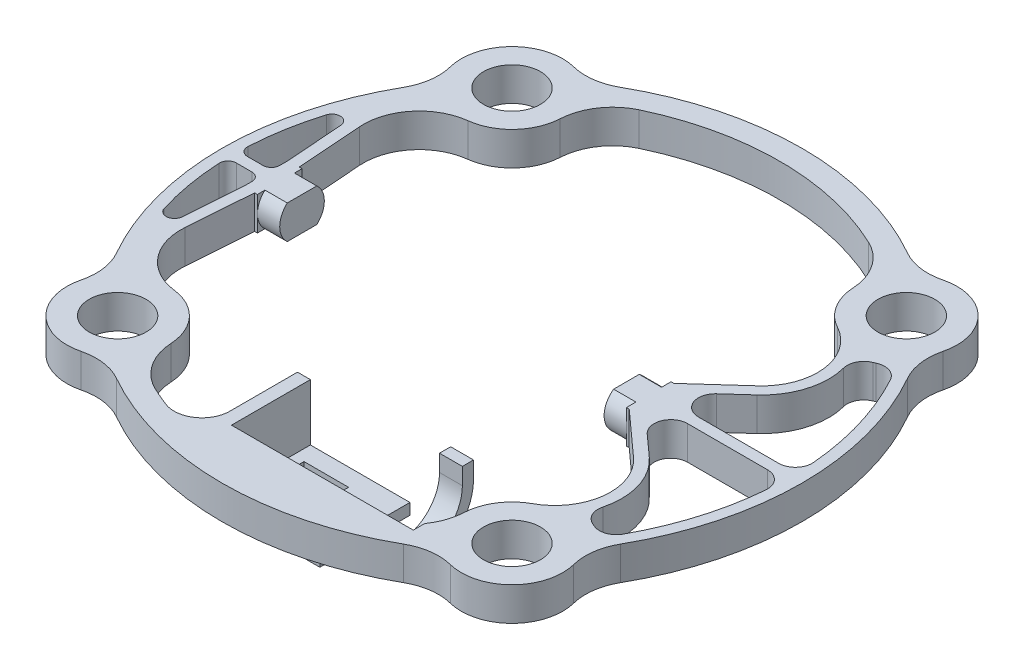
SolidWorks part; units mm, degrees
other "Markup1"
sketch "Sketch20" plane through (52, 6, -52) normal (0.9882, 0.0434, -0.1465) x (-0.1478, 0.0276, -0.9886)
ref_plane "Front Plane" through (0, 0, 0) normal (0, 0, 1) x (1, 0, 0)
ref_plane "Top Plane" through (0, 0, 0) normal (0, 1, 0) x (1, 0, 0)
ref_plane "Right Plane" through (0, 0, 0) normal (1, 0, 0) x (0, 0, -1)
sketch "Sketch1" plane through (0, 0, 0) normal (0, 1, 0) x (1, 0, 0)
  line L1 (-35.3553, -35.3553) -> (35.3553, -35.3553) construction
  line L2 (-35.3553, -35.3553) -> (-35.3553, 35.3553) construction
  line L3 (-35.3553, 35.3553) -> (35.3553, 35.3553) construction
  line L4 (35.3553, -35.3553) -> (35.3553, 35.3553) construction
  line L5 (-35.3553, -35.3553) -> (35.3553, 35.3553) construction
  line L6 (-35.3553, 35.3553) -> (35.3553, -35.3553) construction
  circle A0 centre (0, 0) radius 52
  circle A1 centre (0, 0) radius 48
  circle A2 centre (0, 0) radius 50 construction
  circle A3 centre (35.3553, 35.3553) radius 5.1
  circle A4 centre (-35.3553, 35.3553) radius 5.1
  circle A5 centre (-35.3553, -35.3553) radius 5.1
  circle A6 centre (35.3553, -35.3553) radius 5.1
  circle A7 centre (35.3553, 35.3553) radius 9.1
  circle A8 centre (-35.3553, 35.3553) radius 9.1
  circle A9 centre (-35.3553, -35.3553) radius 9.1
  circle A10 centre (35.3553, -35.3553) radius 9.1
  dimension "D1" = 96
  dimension "D2" = 104
  dimension "D3" = 100
  dimension "D4" = 10.2
  dimension "D5" = 10.2
  dimension "D6" = 10.2
  dimension "D7" = 10.2
  dimension "D8" = 4
extrude "Boss-Extrude1" add sketch "Sketch1" along normal blind 6 contours A8 A1 A7 A0 | A1 A8 A0 A4 | A0 A8 A4 | A0 A8 A1 A4 | A1 A8 A4 | A9 A1 A8 A0 | A1 A9 A5 | A1 A9 A0 A5 | A0 A9 A5 | A0 A9 A1 A5 | A10 A1 A9 A0 | A1 A10 A6 | A0 A10 A1 A6 | A0 A10 A6 | A1 A10 A0 A6 | A10 A0 A7 A1 | A0 A7 A3 | A0 A7 A1 A3 | A1 A7 A0 A3 | A1 A7 A3 region at (49.0102, 0, 15.4585) region at (39.943, 0, -30.075) region at (39.073, 0, -39.073) region at (39.073, 0, 39.073) region at (39.943, 0, 30.075) region at (31.3721, 0, -31.3721) region at (31.3721, 0, 31.3721) region at (30.075, 0, -39.943) region at (0, 0, -48.6096) region at (30.075, 0, 39.943) region at (0, 0, 51.3904) region at (-31.3721, 0, -31.3721) region at (-30.075, 0, -39.943) region at (-39.073, 0, -39.073) region at (-39.073, 0, 39.073) region at (-30.075, 0, 39.943) region at (-31.3721, 0, 31.3721) region at (-41.5843, 0, -27.9071) region at (-39.943, 0, -30.075) region at (-39.943, 0, 30.075)
fillet "Fillet1" radius 10 16 edges at (-27.2586, 3, 39.5091) (-39.5091, 3, 27.2586) (39.5091, 3, 27.2586) (27.2586, 3, 39.5091) (-39.5091, 3, -27.2586) (-27.2586, 3, -39.5091) (27.2586, 3, -39.5091) (39.5091, 3, -27.2586) (-42.5896, 3, 29.8349) (-29.8349, 3, 42.5896) (29.8349, 3, 42.5896) (42.5896, 3, 29.8349) (42.5896, 3, -29.8349) (29.8349, 3, -42.5896) (-29.8349, 3, -42.5896) (-42.5896, 3, -29.8349)
sketch "Sketch2" plane through (0, 6, 0) normal (0, 1, 0) x (1, 0, 0)
  line L0 (-41.15, 11.9734) -> (-41.15, -15.376) construction
  line L1 (24.02, 8.956) -> (24.02, -12.6154) construction
  line L2 (-47.833, 4) -> (47.833, 4) construction
  line L3 (-47.833, -4) -> (47.833, -4) construction
  line L4 (-47.833, 4) -> (-37.65, 4)
  line L5 (-37.65, 4) -> (-37.65, -4)
  line L6 (-37.65, -4) -> (-47.833, -4)
  line L7 (47.833, 4) -> (20.52, 4)
  line L8 (20.52, 4) -> (20.52, -4)
  line L9 (20.52, -4) -> (47.833, -4)
  arc A0 (-43.3702, 20.5675) -> (-43.3702, -20.5675) centre (0, 0) ccw construction
  arc A1 (43.3702, -20.5675) -> (43.3702, 20.5675) centre (0, 0) ccw construction
  arc A2 (-47.833, 4) -> (-47.833, -4) centre (0, 0) ccw
  arc A3 (47.833, 4) -> (47.833, -4) centre (0, 0) cw
  arc M11 (-43.3702, -20.5675) -> (-43.3702, 20.5675) centre (0, 0) cw
  arc M19 (43.3702, 20.5675) -> (43.3702, -20.5675) centre (0, 0) cw
  dimension "D1" = 41.15
  dimension "D2" = 24.02
  dimension "D3" = 4
  dimension "D4" = 4
  dimension "D5" = 3.5
  dimension "D6" = 3.5
extrude "Boss-Extrude2" add sketch "Sketch2" against normal up to surface (6 mm away) contours L6 L5 L4 M11 | L8 L9 L7 M19 region at (-42.7973, 6, 0) region at (34.2322, 6, 0) up to face at (0, 0, 0)
sketch "Sketch3" plane through (0, 6, 0) normal (0, 1, 0) x (1, 0, 0)
  line L0 (-42.15, 4) -> (-42.15, -4)
  line L2 (-47.833, 4) -> (-37.65, 4) construction
  line L3 (-37.65, -4) -> (-47.833, -4) construction
  line L4 (25.02, 4) -> (25.02, -4)
  line L5 (47.833, 4) -> (20.52, 4) construction
  line L6 (20.52, -4) -> (47.833, -4) construction
  line L7 (-37.65, 4) -> (-37.65, -4) construction
  line L8 (20.52, 4) -> (20.52, -4) construction
  line L9 (-42.15, 4) -> (-43.3702, 20.5675)
  line L10 (-42.15, -4) -> (-43.3702, -20.5675)
  line L11 (25.02, 4) -> (43.3702, 20.5675)
  line L12 (25.02, -4) -> (43.3702, -20.5675)
  arc A0 (-43.3702, 20.5675) -> (-43.3702, -20.5675) centre (0, 0) ccw
  arc A1 (43.3702, 20.5675) -> (43.3702, -20.5675) centre (0, 0) cw
  arc A2 (43.3702, -20.5675) -> (47.833, -4) centre (0, 0) ccw construction
  arc M7 (-43.3702, -20.5675) -> (-47.833, -4) centre (0, 0) cw
  line M8 (-47.833, -4) -> (-37.65, -4)
  line M10 (-37.65, 4) -> (-47.833, 4)
  arc M11 (-47.833, 4) -> (-43.3702, 20.5675) centre (0, 0) cw
  arc M19 (43.3702, 20.5675) -> (47.833, 4) centre (0, 0) cw
  line M20 (47.833, 4) -> (20.52, 4)
  line M22 (20.52, -4) -> (47.833, -4)
  arc M23 (47.833, -4) -> (43.3702, -20.5675) centre (0, 0) cw
  dimension "D1" = 4.5
  dimension "D2" = 4.5
extrude "Boss-Extrude3" add sketch "Sketch3" along direction (0, 1, 0) on the side against the normal up to surface (6 mm away) contours L9 M10 M11 | L10 M8 M7 | L11 M20 M19 | L12 M22 M23 region at (-44.6805, 6, -9.9724) region at (-44.6805, 6, 9.9724) region at (39.0615, 6, -9.6497) region at (39.0615, 6, 9.6497) up to face at (-1.4275, 0, 0)
sketch "Sketch4" plane through (0, 6, 0) normal (0, 1, 0) x (1, 0, 0)
  line L0 (-45.0759, 16.4974) -> (-44.3027, 6)
  line L1 (-44.3027, 6) -> (-47.6235, 6)
  line L2 (-47.6235, -6) -> (-44.3027, -6)
  line L3 (-44.3027, -6) -> (-45.0759, -16.4974)
  line L4 (-42.15, -4) -> (-43.3702, -20.5675) construction
  line L5 (-42.15, 4) -> (-43.3702, 20.5675) construction
  line L6 (-42.15, 4) -> (-37.65, 4) construction
  line L7 (-37.65, -4) -> (-42.15, -4) construction
  line L8 (44.2293, 18.6486) -> (30.2197, 6)
  line L9 (30.2197, 6) -> (47.6235, 6)
  line L10 (44.2293, -18.6486) -> (30.2197, -6)
  line L11 (30.2197, -6) -> (47.6235, -6)
  line L12 (25.02, 4) -> (20.52, 4) construction
  line L13 (25.02, 4) -> (43.3702, 20.5675) construction
  line L14 (25.02, -4) -> (43.3702, -20.5675) construction
  line L15 (20.52, -4) -> (25.02, -4) construction
  circle A0 centre (0, 0) radius 48
  dimension "D5" = 96
  dimension "D1" = 2
  dimension "D2" = 2
  dimension "D3" = 2
  dimension "D4" = 2
  dimension "D6" = 2
  dimension "D7" = 2
  dimension "D8" = 2
  dimension "D9" = 2
fillet "Fillet2" radius 10 4 edges at (43.3702, 3, 20.5675) (43.3702, 3, -20.5675) (-43.3702, 3, 20.5675) (-43.3702, 3, -20.5675)
sketch "Sketch5" plane through (0, 6, 0) normal (0, 1, 0) x (1, 0, 0)
  line L0 (32.939, 11.1497) -> (34.2793, 9.6652)
  line L1 (34.2793, 9.6652) -> (27.02, 3.1112)
  line L2 (32.939, -11.1497) -> (34.2793, -9.6652)
  line L3 (34.2793, -9.6652) -> (27.02, -3.1112)
  line L4 (27.02, -3.1112) -> (27.02, 3.1112)
  circle A0 centre (35.3553, 35.3553) radius 9.1
  circle A1 centre (35.3553, -35.3553) radius 9.1
  circle A2 centre (35.3553, -35.3553) radius 11.1
  circle A3 centre (35.3553, 35.3553) radius 11.1
  circle A4 centre (0, 0) radius 50
  circle A5 centre (26.2377, 18.5721) radius 12
  circle A6 centre (26.2377, -18.5721) radius 12
  arc A7 (45.1856, -25.7344) -> (45.1856, 25.7344) centre (0, 0) ccw construction
  arc A8 (32.939, 11.1497) -> (31.0113, 27.3591) centre (26.2377, 18.5721) ccw construction
  arc A9 (31.0113, -27.3591) -> (32.939, -11.1497) centre (26.2377, -18.5721) ccw construction
  dimension "D1" = 2
  dimension "D2" = 2
  dimension "D3" = 2
  dimension "D4" = 2
  dimension "D5" = 2
  dimension "D6" = 2
extrude "Cut-Extrude2" cut sketch "Sketch5" against normal blind 6 contours A6 A2 A4 A3 A5 L1 L4 L3 region at (40.5745, 6, 0)
sketch "Sketch6" plane through (0, 6, 0) normal (0, 1, 0) x (1, 0, 0)
  line L0 (27.02, 0.9819) -> (49.9904, 0.9819)
  line L1 (27.02, -3.1112) -> (27.02, 3.1112) construction
  line L2 (27.02, -1.0181) -> (49.9896, -1.0181)
  line L3 (27.02, 0.9819) -> (27.02, -1.0181)
  line L4 (49.9904, 0.9819) -> (51.1942, 0.9819)
  line L5 (51.1942, 0.9819) -> (51.1942, -1.0181)
  line L6 (51.1942, -1.0181) -> (49.9896, -1.0181)
  arc A0 (42.2845, -26.6837) -> (42.2845, 26.6837) centre (0, 0) ccw construction
  dimension "D1" = 2
extrude "Boss-Extrude4" add sketch "Sketch6" against normal up to surface (6 mm away) up to face at (-35.3553, 0, -30.2553)
fillet "Fillet3" radius 3 8 edges at (27.02, 3, -0.9819) (27.02, 3, 1.0181) (36.7582, 3, 24.3443) (42.2845, 3, 26.6837) (49.9896, 3, 1.0181) (49.9904, 3, -0.9819) (36.7582, 3, -24.3443) (42.2845, 3, -26.6837)
fillet "Fillet4" radius 3 2 edges at (27.02, 3, -3.1112) (27.02, 3, 3.1112)
sketch "Sketch7" plane through (0, 0, 0) normal (0, -1, 0) x (1, 0, 0)
  line L0 (-45.4032, 20.9416) -> (-44.15, 3.9264)
  line L1 (-44.15, 3.9264) -> (-44.15, -3.9264)
  line L2 (-44.15, -3.9264) -> (-45.4032, -20.9416)
  line L3 (-43.0089, -15.6622) -> (-42.15, -4) construction
  line L4 (-43.0089, 15.6622) -> (-42.15, 4) construction
  line L5 (-44.15, 1) -> (-51.4245, 1)
  line L6 (-51.4245, 1) -> (-51.4245, -1)
  line L7 (-51.4245, -1) -> (-44.15, -1)
  circle A0 centre (0, 0) radius 50
  arc A1 (-45.1856, 25.7344) -> (-45.1856, -25.7344) centre (0, 0) ccw construction
  point P14 (-42.5795, 9.8311)
  dimension "D1" = 2
  dimension "D2" = 2
  dimension "D3" = 2
  dimension "D4" = 2
  dimension "D5" = 1
  dimension "D6" = 1
extrude "Cut-Extrude3" cut sketch "Sketch7" against normal blind 6 contours L0 A0 L5 L1 | L7 A0 L2 L1 region at (-46.776, 0, 8.3346) region at (-46.776, 0, -8.3346)
fillet "Fillet5" radius 1.5 8 edges at (-44.15, 3, -3.9264) (-44.15, 3, 3.9264) (-44.15, 3, 1) (-44.15, 3, -1) (-49.99, 3, 1) (-49.99, 3, -1) (-45.4032, 3, -20.9416) (-45.4032, 3, 20.9416)
sketch "Sketch8" plane through (-37.65, 0, 0) normal (1, 0, 0) x (0, 0, -1)
  line L0 (-25.7344, 0) -> (25.7344, 0) construction
  line L2 (-6.5981, 8.7795) -> (6.5981, 8.7795)
  line L3 (-6.5981, 8.7795) -> (-6.5981, -2.7795)
  line L4 (-6.5981, -2.7795) -> (6.5981, -2.7795)
  line L5 (6.5981, 8.7795) -> (6.5981, -2.7795)
  line L6 (-6.5981, 8.7795) -> (6.5981, -2.7795) construction
  line L7 (-6.5981, -2.7795) -> (6.5981, 8.7795) construction
  circle A0 centre (0, 3) radius 4
  dimension "D2" = 8
  dimension "D1" = 3
extrude "Cut-Extrude4" cut sketch "Sketch8" against normal blind 4
sketch "Sketch9" plane through (20.52, 0, 0) normal (-1, 0, 0) x (0, 0, 1)
  line L1 (-6.0027, 9.9205) -> (6.0027, 9.9205)
  line L2 (-6.0027, 9.9205) -> (-6.0027, -4.4662)
  line L3 (-6.0027, -4.4662) -> (6.0027, -4.4662)
  line L4 (6.0027, 9.9205) -> (6.0027, -4.4662)
  line L5 (-6.0027, 9.9205) -> (6.0027, -4.4662) construction
  line L6 (-6.0027, -4.4662) -> (6.0027, 9.9205) construction
  circle A0 centre (0, 2.7271) radius 4
  dimension "D1" = 8
extrude "Cut-Extrude5" cut sketch "Sketch9" against normal blind 4
sketch "Sketch10" plane through (0, 6, 0) normal (0, 1, 0) x (1, 0, 0)
  line L0 (-20.1589, -28) -> (21.0577, -28) construction
  line L1 (-20.1589, -42.15) -> (16.3069, -42.15) construction
  line L2 (-8.15, -28) -> (-8.15, -45.3576) construction
  line L3 (-10.4647, -28) -> (-10.4647, -46.8454)
  line L4 (-8.15, -42.15) -> (14.7, -42.15)
  line L5 (-8.15, -42.15) -> (-8.15, -28)
  line L6 (-8.15, -28) -> (14.7, -28)
  line L7 (14.7, -42.15) -> (14.7, -28)
  line L8 (14.7, -42.15) -> (18.95, -42.15)
  line L9 (14.7, -42.15) -> (14.7, -28)
  line L10 (14.7, -28) -> (18.95, -28)
  line L11 (18.95, -42.15) -> (18.95, -28)
  line L12 (-10.4647, -28) -> (-8.15, -28)
  line L13 (-8.15, -28) -> (-8.15, -42.15)
  line L14 (-8.15, -42.15) -> (18.95, -42.15)
  line L15 (18.95, -42.15) -> (18.95, -44.101)
  arc A0 (-20.5675, -43.3702) -> (20.5675, -43.3702) centre (0, 0) ccw construction
  arc A1 (-10.4647, -46.8454) -> (18.95, -44.101) centre (0, 0) ccw
  dimension "D1" = 28
  dimension "D2" = 14.15
  dimension "D3" = 8.15
  dimension "D4" = 22.85
  dimension "D5" = 4.25
extrude "Boss-Extrude5" add sketch "Sketch10" along direction (0, 1, 0) on the side against the normal up to surface (6 mm away) contours L3 A1 L15 L8 L4 L5 L12 region at (0.632, 6, 42.9201) up to face at (-46.1845, 0, -5.5419)
sketch "Sketch11" plane through (0, 0, 0) normal (0, -1, 0) x (1, 0, 0)
  line L0 (-8.15, 28) -> (-8.15, 42.15) construction
  line L1 (-10.4647, 28) -> (-8.15, 28)
  line L2 (-10.4647, 28) -> (-10.4647, 42.15)
  line L3 (-10.4647, 42.15) -> (-8.15, 42.15)
  line L4 (-8.15, 28) -> (-8.15, 42.15)
  line L5 (-10.4647, 42.15) -> (9.7, 42.15)
  line L6 (-10.4647, 42.15) -> (-10.4647, 44.15)
  line L7 (-10.4647, 44.15) -> (9.7, 44.15)
  line L8 (9.7, 42.15) -> (9.7, 44.15)
  dimension "D1" = 2
  dimension "D2" = 17.85
extrude "Boss-Extrude6" add sketch "Sketch11" along normal blind 6.15 contours L5 L8 L7 L6 L3 | L1 L4 L3 L2 region at (-9.3073, 0, 35.075) region at (-0.3823, 0, 43.15)
sketch "Sketch12" plane through (18.95, 0, 0) normal (1, 0, 0) x (0, 0, -1)
  line L0 (-42.15, -6.15) -> (-42.15, 0) construction
  line L1 (-44.15, 3) -> (-25.85, 3)
  circle A0 centre (-35, 3) radius 7.15
  circle A1 centre (-35, 3) radius 9.15
  line M2 (-44.101, 0) -> (-42.15, 0)
  line M3 (-42.15, 0) -> (-42.15, 6)
  dimension "D2" = 14.3
  dimension "D3" = 2
  dimension "D1" = 7.15
extrude "Boss-Extrude7" add sketch "Sketch12" against normal blind 4.1 contours A1 L1 A0 M2 M3 region at (18.95, 2.7999, 26.85)
sketch "Sketch13" plane through (0, 6, 0) normal (0, 1, 0) x (1, 0, 0)
  line L0 (18.95, -42.15) -> (24.1394, -42.15)
  line L1 (24.1394, -42.15) -> (18.95, -46.449)
  line L2 (18.95, -46.449) -> (18.95, -42.15)
extrude "Boss-Extrude8" add sketch "Sketch13" against normal blind 6
sketch "Sketch14" plane through (0, 3, 0) normal (0, 1, 0) x (1, 0, 0)
  line L1 (14.85, -25.85) -> (18.95, -25.85)
  line L2 (14.85, -25.85) -> (14.85, -27.85)
  line L3 (14.85, -27.85) -> (18.95, -27.85)
  line L4 (18.95, -25.85) -> (18.95, -27.85)
extrude "Boss-Extrude9" add sketch "Sketch14" along normal blind 3
sketch "Sketch15" plane through (-8.15, 0, 0) normal (1, 0, 0) x (0, 0, -1)
  line L0 (-28, -6.15) -> (-28, 6) construction
  line L1 (-42.15, -6.15) -> (-28, -6.15)
  line L2 (-42.15, -6.15) -> (-42.15, -4.15)
  line L3 (-42.15, -4.15) -> (-28, -4.15)
  line L4 (-28, -6.15) -> (-28, -4.15)
  dimension "D1" = 2
extrude "Boss-Extrude10" add sketch "Sketch15" along normal blind 17.85
sketch "Sketch16" plane through (0, -6.15, 0) normal (0, -1, 0) x (-1, 0, 0)
  line L0 (10.4647, -28) -> (-9.7, -28) construction
  line L1 (-9.7, -42.15) -> (-4.7, -42.15)
  line L2 (-9.7, -42.15) -> (-9.7, -28)
  line L3 (-9.7, -28) -> (-4.7, -28)
  line L4 (-4.7, -42.15) -> (-4.7, -28)
  dimension "D1" = 5
extrude "Boss-Extrude11" add sketch "Sketch16" along normal blind 2.25
sketch "Sketch17" plane through (9.7, 0, 0) normal (1, 0, 0) x (0, 0, -1)
  line L0 (-28, -4.15) -> (-42.15, -4.15) construction
  circle A0 centre (-35.4211, -6.275) radius 1.5
  dimension "D2" = 3
  dimension "D1" = 2.125
extrude "Cut-Extrude6" cut sketch "Sketch17" against normal blind 3.5
sketch "Sketch18" plane through (9.7, 0, 0) normal (1, 0, 0) x (0, 0, -1)
  line L0 (-42.15, -6.15) -> (-28, -6.15)
  line L2 (-42.15, -6.15) -> (-28, -6.15)
  line L3 (-42.15, -6.15) -> (-42.15, -8.4)
  line L4 (-42.15, -8.4) -> (-28, -8.4)
  line L5 (-28, -6.15) -> (-28, -8.4)
  circle A0 centre (-35.4211, -6.275) radius 2.125
  line M5 (-42.15, -6.15) -> (-42.15, -8.4)
  line M6 (-42.15, -8.4) -> (-28, -8.4)
  line M7 (-28, -8.4) -> (-28, -4.15)
extrude "Cut-Extrude7" cut sketch "Sketch18" against normal blind 5.5 contours A0 L0 M5 M6 | A0 L4 L2 M7 region at (9.7, -7.3306, 39.6105) region at (9.7, -7.3239, 30.8829)
fillet "Fillet6" radius 5 2 edges at (7.2, -6.15, 37.5424) (7.2, -6.15, 33.2998)
fillet "Fillet7" radius 5 1 edges at (-0.3823, 0, 44.15)
fillet "Fillet8" radius 5 1 edges at (-10.4647, 3, 46.8454)
sketch "Sketch19" plane through (0, 6, 0) normal (0, 1, 0) x (1, 0, 0)
  line L0 (-8.15, -42.15) -> (22.5214, -42.15) construction
  line L1 (18.95, -25.85) -> (24.45, -25.85)
  line L2 (18.95, -25.85) -> (18.95, -42.15)
  line L3 (18.95, -42.15) -> (24.45, -42.15)
  line L4 (24.45, -25.85) -> (24.45, -42.15)
  dimension "D1" = 0
  dimension "D2" = 5.5
extrude "Cut-Extrude8" cut sketch "Sketch19" against normal blind 13.5
fillet "Fillet9" radius 5 1 edges at (16.9, 0, 43.6442)
sketch "Sketch21" plane through (0, -4.15, 0) normal (0, 1, 0) x (1, 0, 0)
  line L1 (-6.15, -39.15) -> (1.85, -39.15)
  line L2 (-6.15, -39.15) -> (-6.15, -31.15)
  line L3 (-6.15, -31.15) -> (1.85, -31.15)
  line L4 (1.85, -39.15) -> (1.85, -31.15)
  line L5 (-6.15, -39.15) -> (1.85, -31.15) construction
  line L6 (-6.15, -31.15) -> (1.85, -39.15) construction
  line L8 (-8.15, -42.15) -> (24.45, -42.15) construction
  line L9 (-8.15, -42.15) -> (-8.15, -28) construction
  point P0 (-2.15, -35.15)
  dimension "D1" = 8
  dimension "D2" = 7
  dimension "D3" = 8
  dimension "D4" = 6
extrude "Cut-Extrude9" cut sketch "Sketch21" against normal through all
